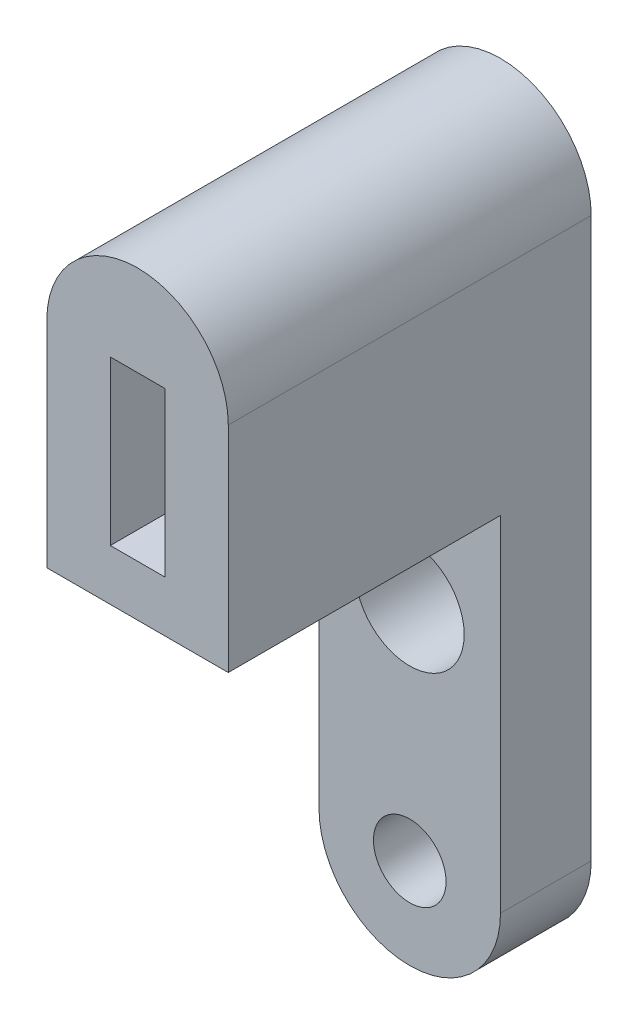
SolidWorks part; units mm, degrees
ref_plane "Front Plane" through (0, 0, 0) normal (0, 0, 1) x (1, 0, 0)
ref_plane "Top Plane" through (0, 0, 0) normal (0, 1, 0) x (1, 0, 0)
ref_plane "Right Plane" through (0, 0, 0) normal (1, 0, 0) x (0, 0, -1)
sketch "Sketch1" plane through (0, 0, 0) normal (0, 0, 1) x (1, 0, 0)
  line L0 (0, -17.7121) -> (0, 13.0879) construction
  line L3 (-1.5, 4.0879) -> (1.5, 4.0879)
  line L4 (-1.5, 4.0879) -> (-1.5, 13.0879)
  line L5 (-1.5, 13.0879) -> (1.5, 13.0879)
  line L6 (1.5, 4.0879) -> (1.5, 13.0879)
  line L7 (-1.5, 4.0879) -> (1.5, 13.0879) construction
  line L8 (-1.5, 13.0879) -> (1.5, 4.0879) construction
  line L9 (-5, -17.7121) -> (-5, 13.0879)
  line L10 (5, -17.7121) -> (5, 13.0879)
  line L11 (-5, 1.2763) -> (5, 1.2763)
  circle A1 centre (0, -5.4121) radius 3
  circle A2 centre (0, -17.7121) radius 2
  arc A5 (-5, -17.7121) -> (5, -17.7121) centre (0, -17.7121) ccw
  arc A6 (5, 13.0879) -> (-5, 13.0879) centre (0, 13.0879) ccw
  point P0 (0, 8.5879)
  point P1 (0, -2.3121)
  dimension "D1" = 4
  dimension "D2" = 6
  dimension "D3" = 9
  dimension "D5" = 7.3
  dimension "D6" = 6.5
  dimension "D4" = 3
  dimension "D7" = 10
extrude "Boss-Extrude1" add sketch "Sketch1" along normal blind 5 contours L9 A5 L10 L11 A1 A2 | L10 A6 L9 L11 L6 L3 L4 L5 region at (0, -10.428, 0) region at (-4.8044, 7.1821, 0)
extrude "Boss-Extrude2" add sketch "Sketch1<4>" along normal blind 20 contours L10 A6 L9 L11 L6 L3 L4 L5 region at (-4.8044, 7.1821, 0)
sketch "Sketch1<4>" plane through (0, 0, 0) normal (0, 0, 1) x (1, 0, 0) same geometry as "Sketch1"
